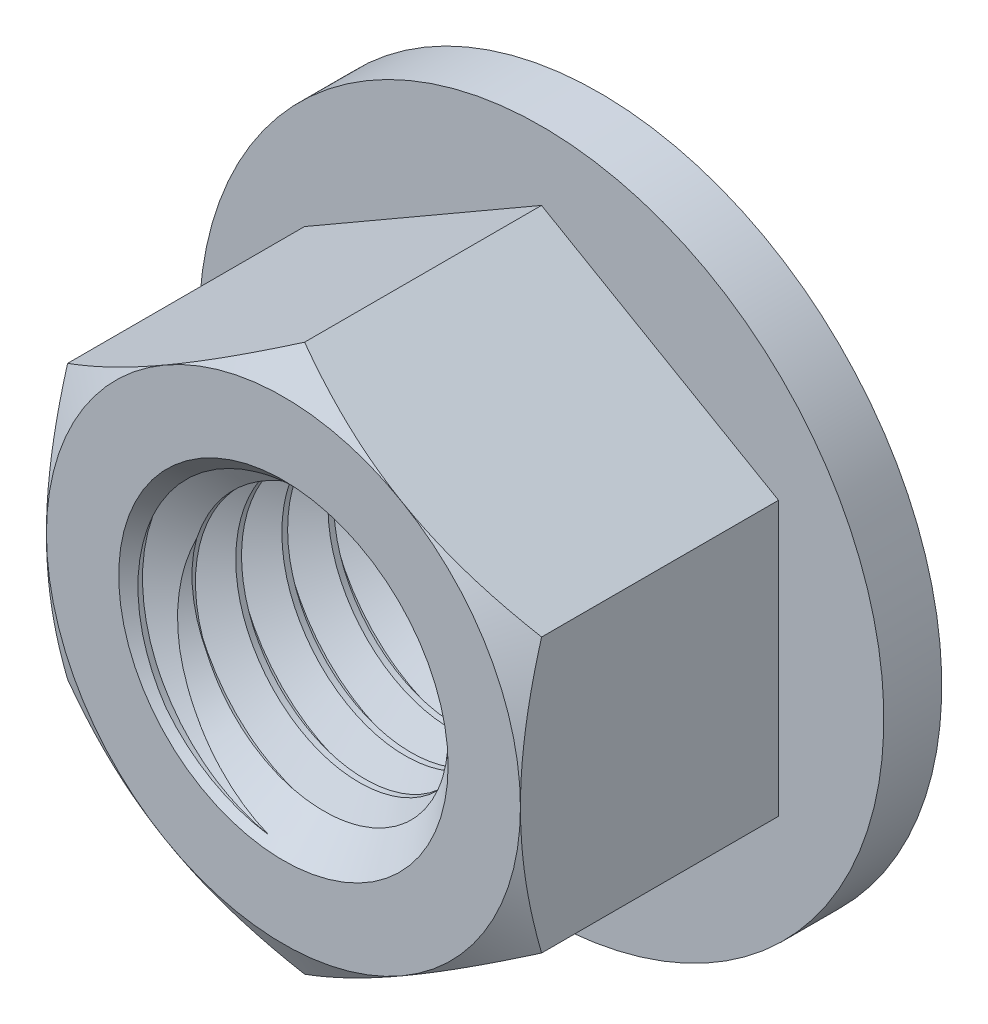
SolidWorks part; units mm, degrees
ref_plane "Front Plane" through (0, 0, 0) normal (0, 0, 1) x (1, 0, 0)
ref_plane "Top Plane" through (0, 0, 0) normal (0, 1, 0) x (1, 0, 0)
ref_plane "Right Plane" through (0, 0, 0) normal (1, 0, 0) x (0, 0, -1)
sketch "Sketch1" plane through (0, 0, 0) normal (0, 0, 1) x (1, 0, 0)
  line L1 (0, 10.3923) -> (-9, 5.1962)
  line L2 (-9, 5.1962) -> (-9, -5.1962)
  line L3 (-9, -5.1962) -> (0, -10.3923)
  line L4 (0, -10.3923) -> (9, -5.1962)
  line L5 (9, -5.1962) -> (9, 5.1962)
  line L6 (9, 5.1962) -> (0, 10.3923)
  circle A0 centre (0, 0) radius 9 construction
  dimension "Hex" = 18
extrude "Extrude1" add sketch "Sketch1" against normal blind 12
sketch "Sketch13" plane through (0, 0, -12) normal (0, 0, -1) x (-1, 0, 0)
  circle A0 centre (0, 0) radius 13
  dimension "Flange od" = 26
extrude "Extrude3" add sketch "Sketch13" against normal blind 2.2
sketch "Sketch2" plane through (0, 0, 0) normal (0, 0, 1) x (1, 0, 0)
  circle A0 centre (0, 0) radius 9 construction
  circle A1 centre (0, 0) radius 9
extrude "Cut-Extrude1" cut sketch "Sketch2" against normal through all draft 60 flip side to cut
sketch "Sketch4" plane through (0, 0, 0) normal (0, 0, 1) x (1, 0, 0)
  circle A0 centre (0, 0) radius 6
  dimension "Thread Dia" = 12
extrude "Cut-Extrude3" cut sketch "Sketch4" against normal through all
sketch "Sketch7" plane through (0, 0, 0) normal (0, 0, 1) x (1, 0, 0)
  circle A4 centre (0, 0) radius 6.254
  circle A5 centre (0, 0) radius 6.254
  dimension "D1" = 0.254
sketch "Sketch8" plane through (0, 0, -12) normal (0, 0, -1) x (-1, 0, 0)
  circle A1 centre (0, 0) radius 6.254
  circle A2 centre (0, 0) radius 6.254 construction
sketch "Sketch5" plane through (0, 0, 0) normal (0, 0, 1) x (1, 0, 0)
  circle A0 centre (0, 0) radius 6 construction
  circle A1 centre (0, 0) radius 6
curve "Helix/Spiral1" pitch 1.75 height 13.75 turns 7.8571 parameters "pitch"=1.75
sketch "Sketch9" plane through (0, 0, 0) normal (1, 0, 0) x (0, 0, -1)
  line L0 (-0.875, 6) -> (-0.6562, 6)
  line L1 (-0.6562, 6) -> (0, 4.8633)
  line L2 (-0.875, 6) -> (-1.5312, 4.8633)
  line L3 (-1.5312, 4.8633) -> (0, 4.8633)
  line L4 (-0.7656, 6) -> (-0.7656, 4.8633) construction
  line L5 (-1.2031, 5.4317) -> (-0.3281, 5.4317) construction
  line L7 (0, 4.8633) -> (0, 6) construction
  line L8 (0, 6) -> (0, -6) construction
  dimension "D1" = 0.2188
  dimension "D2" = 0.875
  dimension "D3" = 60
sketch "Sketch12" plane through (0, 0, 0) normal (0, 0, 1) x (1, 0, 0)
  circle A0 centre (0, 0) radius 4.8633
  circle A1 centre (0, 0) radius 6 construction
  circle A2 centre (0, 0) radius 6
extrude "Extrude2" add sketch "Sketch12" against normal up to surface (12 mm away)
sweep "Cut-Sweep1" cut profiles "Sketch9" path "Helix/Spiral1"
extrude "Cut-Extrude6" cut sketch "Sketch7" against normal through all draft 45
extrude "Cut-Extrude7" cut sketch "Sketch8" against normal through all draft 45
equation "\"D2@Sketch9\" = \"pitch@Helix/Spiral1\"*.5"
equation "\"D3@Helix/Spiral1\" = \"pitch@Helix/Spiral1\"+\"Height@Extrude1\""
equation "\"D1@Sketch9\" = \"pitch@Helix/Spiral1\"*.125"
